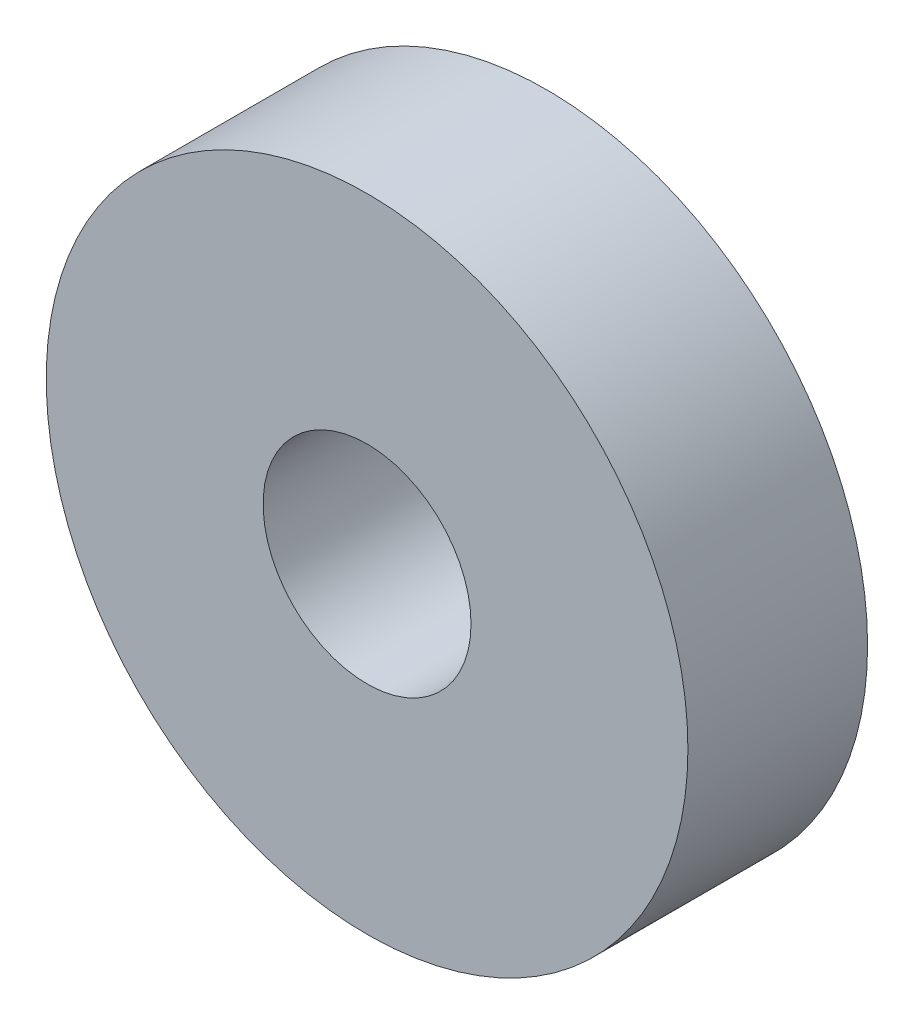
SolidWorks part; units mm, degrees
material "Beech"
ref_plane "Front Plane" through (0, 0, 0) normal (0, 0, 1) x (1, 0, 0)
ref_plane "Top Plane" through (0, 0, 0) normal (0, 1, 0) x (1, 0, 0)
ref_plane "Right Plane" through (0, 0, 0) normal (1, 0, 0) x (0, 0, -1)
sketch "Sketch1" plane through (0, 0, 0) normal (0, 0, 1) x (1, 0, 0)
  circle A0 centre (0, 0) radius 1.0287
  circle A1 centre (0, 0) radius 3.175
  dimension "D1" = 6.35
  dimension "D2" = 2.0574
extrude "Boss-Extrude1" add sketch "Sketch1" along normal blind 1.778
